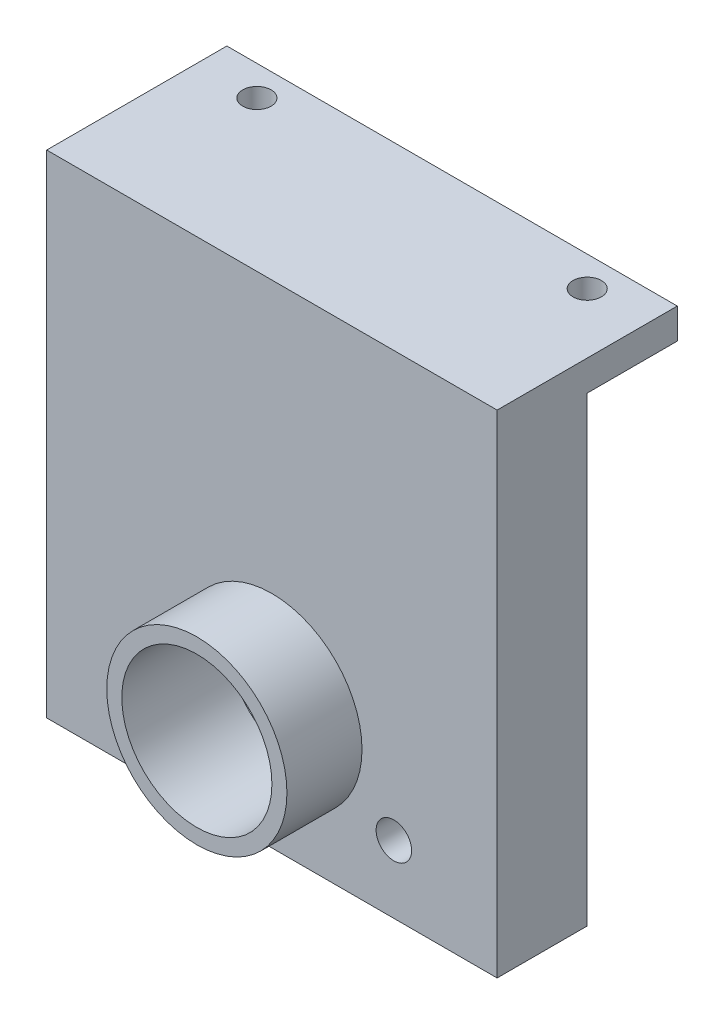
SolidWorks part; units mm, degrees
ref_plane "Front Plane" through (0, 0, 0) normal (0, 0, 1) x (1, 0, 0)
ref_plane "Top Plane" through (0, 0, 0) normal (0, 1, 0) x (1, 0, 0)
ref_plane "Right Plane" through (0, 0, 0) normal (1, 0, 0) x (0, 0, -1)
sketch "Sketch2" plane through (0, 0, 0) normal (0, 0, 1) x (1, 0, 0)
  line L6 (-16.51, 36.5252) -> (-16.51, 2.54)
  line L7 (-16.51, 2.54) -> (16.51, 2.54)
  line L8 (16.51, 2.54) -> (16.51, 36.5252)
  line L9 (19.05, 41.6052) -> (19.05, 0)
  line L10 (-19.05, 0) -> (19.05, 0)
  line L11 (-19.05, 41.6052) -> (-19.05, 0)
  line L13 (-19.05, 41.6052) -> (19.05, 41.6052)
  line L14 (-16.51, 36.5252) -> (16.51, 36.5252)
  point P2 (-16.51, 39.0652)
  point P6 (0, 0)
  point P11 (-21.4792, 36.5252)
extrude "Boss-Extrude1" add sketch "Sketch2" along normal blind 5.08
sketch "Sketch4" plane through (0, 0, 0) normal (0, 0, -1) x (-1, 0, 0)
  line L0 (-19.05, 41.6052) -> (19.05, 41.6052) construction
  line L1 (-19.05, 41.6052) -> (19.05, 41.6052)
  line L2 (-19.05, 41.6052) -> (-19.05, 39.0362)
  line L3 (-19.05, 0) -> (-19.05, 41.6052) construction
  line L4 (-19.05, 39.0362) -> (19.05, 39.0652)
  line L5 (19.05, 41.6052) -> (19.05, 0) construction
  line L7 (19.05, 39.0652) -> (19.05, 41.6052)
extrude "Boss-Extrude2" add sketch "Sketch4" along normal blind 7.62
hole_wizard "M2 Clearance Hole1" positions "Sketch5" profile "Sketch6" hole size "M2" standard "ANSI Metric" end condition through all
sketch "Sketch5" plane through (0, 41.6052, 0) normal (0, 1, 0) x (1, 0, 0)
  line L0 (19.05, 0) -> (-19.05, 0) construction
  line L1 (19.05, -5.08) -> (19.05, 7.62) construction
  line L2 (-19.05, -5.08) -> (-19.05, 7.62) construction
  line L4 (-13.97, 5.08) -> (13.97, 5.08) construction
  point P0 (-13.97, 5.08)
  point P2 (13.97, 5.08)
  point P18 (0, 5.08)
  point P19 (0, 0)
  point P20 (13.97, 5.08)
  dimension "D1" = 5.08
  dimension "D2" = 5.08
sketch "Sketch6" plane through (-13.97, 41.6052, -5.08) normal (1, 0, 0) x (0, 0, 1)
  line L0 (0, 0) -> (0, 41.6052)
  line L1 (0, 41.6052) -> (1.2, 41.6052)
  line L2 (1.2, 41.6052) -> (1.2, 0)
  line L5 (1.2, 0) -> (0, 0)
  line L11 (0, -6.35) -> (0, 107.95) construction
  dimension "Thru Hole Dia." = 2.4
  dimension "Thru Hole Depth" = 41.6052
sketch "Sketch7" plane through (0, 0, 5.08) normal (0, 0, 1) x (1, 0, 0)
  line L12 (-10.3149, 5.715) -> (10.3149, 5.715) construction
  line L13 (-19.05, 0) -> (19.05, 0) construction
  circle A0 centre (-10.3149, 5.715) radius 1.5011
  circle A1 centre (10.3149, 5.715) radius 1.5011
  point P2 (-10.9861, 5.715)
  point P12 (-8.1457, 8.0007)
  point P13 (0, 5.715)
  point P15 (14.0263, 7.8248)
  dimension "D1" = 3.0023
  dimension "D3" = 20.6299
  dimension "D2" = 5.715
sketch "Sketch8" plane through (0, 0, 5.08) normal (0, 0, 1) x (1, 0, 0)
  line L1 (0, 11.0261) -> (0, 0) construction
  line L2 (-16.51, 4.6761) -> (16.51, 4.6761) construction
  line L3 (-16.51, 36.5252) -> (-16.51, 2.54) construction
  line L4 (16.51, 2.54) -> (16.51, 36.5252) construction
  line L5 (-19.05, 0) -> (19.05, 0) construction
  line L6 (19.05, 0) -> (19.05, 41.6052) construction
  line L7 (19.05, 41.6052) -> (-19.05, 41.6052) construction
  line L8 (-19.05, 41.6052) -> (-19.05, 0) construction
  line L9 (-19.05, 0) -> (19.05, 0)
  line L10 (19.05, 0) -> (19.05, 41.6052)
  line L11 (19.05, 41.6052) -> (-19.05, 41.6052)
  line L12 (-19.05, 41.6052) -> (-19.05, 0)
  circle A0 centre (0, 11.0261) radius 6.35
  dimension "D1" = 12.7
  dimension "D2" = 11.0261
extrude "Boss-Extrude3" add sketch "Sketch8" along normal blind 2.54
extrude "Cut-Extrude1" cut sketch "Sketch7" against normal through all both and the other way through all
sketch "Sketch9" plane through (0, 0, 7.62) normal (0, 0, 1) x (1, 0, 0)
  circle A1 centre (0, 11.0261) radius 6.35 construction
  circle A2 centre (0, 11.0261) radius 7.62
  circle A3 centre (0, 11.0261) radius 7.62
  circle A4 centre (0, 11.0261) radius 6.35
  dimension "D1" = 1.27
extrude "Boss-Extrude4" add sketch "Sketch9" along normal blind 6.35
equation "\"D1@Sketch7\"=2*0.0591in"
